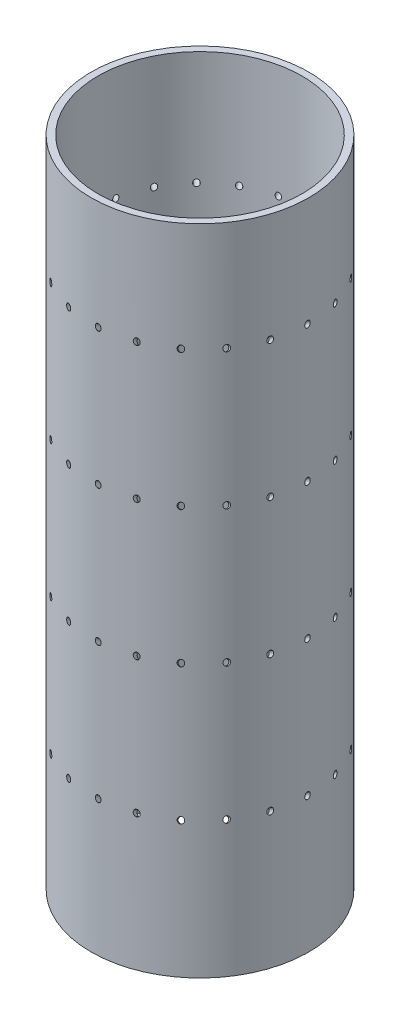
SolidWorks part; units mm, degrees
ref_plane "Front" through (0, 0, 0) normal (0, 0, 1) x (1, 0, 0)
ref_plane "Top" through (0, 0, 0) normal (0, 1, 0) x (1, 0, 0)
ref_plane "Right" through (0, 0, 0) normal (1, 0, 0) x (0, 0, -1)
sketch "Sketch1" plane through (0, 0, 0) normal (0, 1, 0) x (1, 0, 0)
  circle A0 centre (0, 0) radius 47.625
  circle A1 centre (0, 0) radius 50.8
  dimension "D1" = 95.25
  dimension "D2" = 3.175
extrude "Boss-Extrude1" add sketch "Sketch1" along normal blind 304.8
sketch "Sketch2" plane through (0, 0, 0) normal (0, 0, 1) x (1, 0, 0)
  line L0 (50.8, 254) -> (61.2032, 261.2844)
  line L1 (50.8, 0) -> (50.8, 304.8) construction
  line L2 (50.8, 254) -> (40.3968, 246.7156)
  line L3 (50.8, 254) -> (113.5408, 254) construction
  line L4 (50.8, 304.8) -> (-50.8, 304.8) construction
  dimension "D1" = 35
  dimension "D2" = 25.4
  dimension "D3" = 50.8
ref_plane "Plane2" through (61.2032, 261.2844, 0) normal (0.8192, 0.5736, 0) x (0, 0, -1)
sketch "Sketch4" plane through (61.2032, 261.2844, 0) normal (0.8192, 0.5736, 0) x (0, 0, -1)
  circle A0 centre (-0.6144, 0) radius 1.27
  dimension "D1" = 2.54
extrude "Cut-Extrude1" cut sketch "Sketch4" against normal up to next
pattern_circular "CirPattern1" count 21 over 360 about axis through (0, 304.8, 0) along (0, 1, 0) of "Cut-Extrude1"
pattern_linear "LPattern2" count 4 spacing 63.5 along (0, -1, 0) of "CirPattern1"
